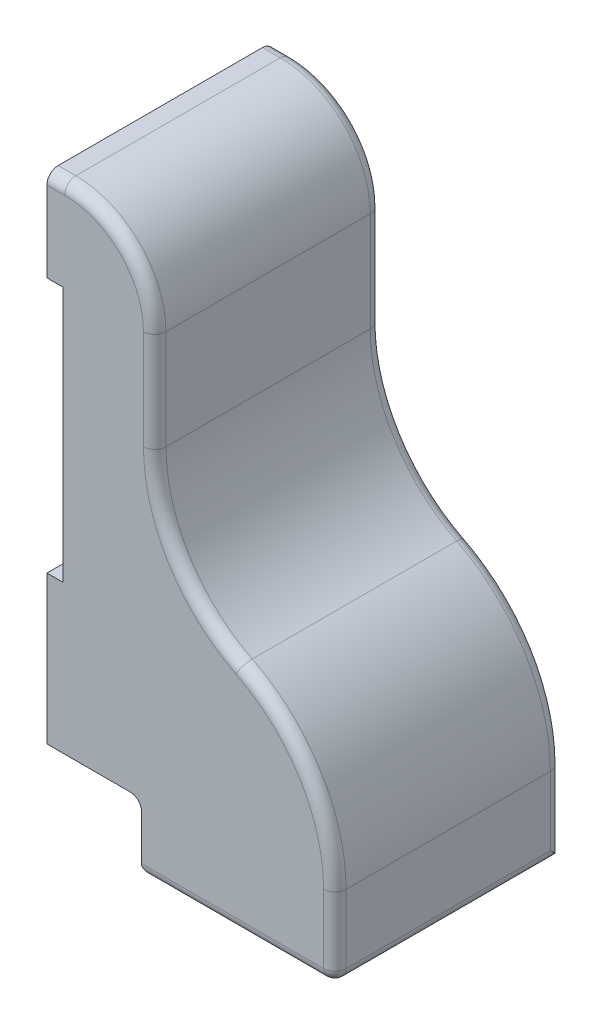
SolidWorks part; units mm, degrees
material "ABS"
ref_plane "X-Y Datum" through (0, 0, 0) normal (0, 0, 1) x (1, 0, 0)
ref_plane "X-Z Datum" through (0, 0, 0) normal (0, 1, 0) x (1, 0, 0)
ref_plane "Y-Z Datum" through (0, 0, 0) normal (1, 0, 0) x (0, 0, -1)
sketch "Sketch1" plane through (0, 0, 0) normal (1, 0, 0) x (0, 0, -1)
  line L0 (100.5047, -7.0485) -> (113.2047, 7.0485)
  line L1 (113.2047, -7.0485) -> (100.5047, 7.0485)
  line L3 (79.8672, -15.875) -> (133.8422, -15.875)
  line L4 (79.8672, -15.875) -> (79.8672, 15.875)
  line L5 (79.8672, 15.875) -> (133.8422, 15.875)
  line L6 (133.8422, -15.875) -> (133.8422, 15.875)
  line L7 (79.8672, -15.875) -> (133.8422, 15.875) construction
  line L8 (79.8672, 15.875) -> (133.8422, -15.875) construction
  point P4 (106.8547, 0)
  dimension "D1" = 31.75
  dimension "D2" = 53.975
extrude "Boss-Extrude1" add sketch "Sketch1" along normal blind 76.2
shell "Shell1" thickness 5
sketch "Sketch2" plane through (0, -20.875, 0) normal (0, -1, 0) x (-1, 0, 0)
  line L0 (-76.2, 133.8422) -> (0, 133.8422) construction
  line L1 (-76.2, 79.8672) -> (-76.2, 133.8422) construction
  line L2 (-76.2, 79.8672) -> (0, 79.8672) construction
  line L3 (-76.2, 133.8422) -> (0, 133.8422)
  line L4 (-76.2, 79.8672) -> (-76.2, 133.8422)
  line L5 (-76.2, 79.8672) -> (0, 79.8672)
  line L6 (-31.75, 79.8672) -> (-31.75, 133.8422)
  dimension "D1" = 44.45
extrude "Cut-Extrude1" cut sketch "Sketch2" against normal blind 5 contours L5 L6 L3 L4
fillet "Fillet2" radius 6.35 1 edges at (31.75, -15.875, -106.8547)
sketch "Sketch3" plane through (0, -20.875, 0) normal (0, -1, 0) x (1, 0, 0)
  line L0 (31.75, -79.8672) -> (31.75, -133.8422) construction
  line L1 (76.2, -79.8672) -> (31.75, -79.8672) construction
  line L2 (76.2, -79.8672) -> (76.2, -133.8422) construction
  line L3 (76.2, -133.8422) -> (31.75, -133.8422) construction
  line L4 (0, -138.8422) -> (81.2, -138.8422)
  line L5 (81.2, -138.8422) -> (81.2, -74.8672)
  line L6 (81.2, -74.8672) -> (0, -74.8672)
  line L7 (0, -74.8672) -> (0, -138.8422)
  line L8 (0, -138.8422) -> (81.2, -138.8422)
  line L9 (81.2, -138.8422) -> (81.2, -74.8672)
  line L10 (81.2, -74.8672) -> (0, -74.8672)
  line L11 (0, -74.8672) -> (0, -138.8422)
  line L12 (76.2, -79.8672) -> (31.75, -79.8672)
  line L13 (31.75, -79.8672) -> (31.75, -133.8422)
  line L14 (76.2, -133.8422) -> (31.75, -133.8422)
  line L15 (76.2, -79.8672) -> (76.2, -133.8422)
  line L16 (26.67, -138.8422) -> (26.67, -74.8672)
  dimension "D2" = 5
  dimension "D3" = 5.08
  dimension "D1" = 0
extrude "Boss-Extrude2" add sketch "Sketch3" along normal blind 19.05
fillet "Fillet5" radius 3.175 1 edges at (26.67, -20.875, -106.8547)
fillet "Fillet6" radius 3.175 2 edges at (26.67, -39.925, -106.8547) (53.935, -39.925, -74.8672)
sketch "Sketch4" plane through (0, 0, 0) normal (1, 0, 0) x (0, 0, -1)
  line L0 (113.2047, -7.0485) -> (100.5047, 7.0485) construction
  line L1 (100.5047, -7.0485) -> (113.2047, 7.0485) construction
  line L2 (113.2047, -7.0485) -> (100.5047, 7.0485)
  line L3 (100.5047, -7.0485) -> (113.2047, 7.0485)
  line L4 (79.8672, -15.875) -> (133.8422, -15.875)
  line L5 (133.8422, -15.875) -> (133.8422, 15.875)
  line L6 (133.8422, 15.875) -> (79.8672, 15.875)
  line L7 (79.8672, 15.875) -> (79.8672, -15.875)
  line L8 (79.8672, -15.875) -> (133.8422, -15.875)
  line L9 (133.8422, -15.875) -> (133.8422, 15.875)
  line L10 (133.8422, 15.875) -> (79.8672, 15.875)
  line L11 (79.8672, 15.875) -> (79.8672, -15.875)
  line L12 (87.2421, 105.9053) -> (126.4673, 105.9053) construction
  line L14 (79.8672, 97.9678) -> (133.8422, 97.9678)
  line L15 (79.8672, 97.9678) -> (79.8672, 113.8428)
  line L16 (79.8672, 113.8428) -> (133.8422, 113.8428)
  line L17 (133.8422, 97.9678) -> (133.8422, 113.8428)
  line L18 (79.8672, 97.9678) -> (133.8422, 113.8428) construction
  line L19 (79.8672, 113.8428) -> (133.8422, 97.9678) construction
  point P10 (106.8547, 105.9053)
  point P15 (0, 0)
  dimension "D2" = 15.875
  dimension "D1" = 0
extrude "Boss-Extrude3" add sketch "Sketch4" along normal blind 25.4 separate body contours L14 L17 L16 L15
shell "Shell2" thickness 5
sketch "Sketch5" plane through (0, 92.9678, 0) normal (0, -1, 0) x (1, 0, 0)
  line L4 (9.525, -74.8672) -> (9.525, -138.8422)
  line L5 (30.4, -138.8422) -> (0, -138.8422) construction
  line L6 (25.4, -133.8422) -> (0, -133.8422) construction
  line L7 (25.4, -133.8422) -> (0, -133.8422)
  line L8 (25.4, -79.8672) -> (25.4, -133.8422) construction
  line L9 (25.4, -79.8672) -> (25.4, -133.8422)
  line L10 (25.4, -79.8672) -> (0, -79.8672) construction
  line L11 (25.4, -79.8672) -> (0, -79.8672)
  line L12 (30.4, -74.8672) -> (0, -74.8672) construction
  point P0 (0, 0)
  dimension "D1" = 15.875
extrude "Cut-Extrude2" cut sketch "Sketch5" against normal blind 5 contours L9 L11 L4 L7
sketch "Sketch6" plane through (0, 92.9678, 0) normal (0, -1, 0) x (1, 0, 0)
  line L0 (30.4, -74.8672) -> (0, -74.8672) construction
  line L1 (30.4, -138.8422) -> (4.525, -138.8422)
  line L2 (30.4, -138.8422) -> (30.4, -74.8672)
  line L3 (30.4, -74.8672) -> (4.525, -74.8672)
  line L4 (4.525, -138.8422) -> (4.525, -74.8672)
  line L5 (9.525, -79.8672) -> (9.525, -133.8422) construction
  line L6 (25.4, -133.8422) -> (9.525, -133.8422) construction
  line L7 (25.4, -79.8672) -> (25.4, -133.8422) construction
  line L8 (25.4, -79.8672) -> (9.525, -79.8672) construction
  line L9 (25.4, -133.8422) -> (9.525, -133.8422)
  line L10 (25.4, -79.8672) -> (25.4, -133.8422)
  line L11 (25.4, -79.8672) -> (9.525, -79.8672)
  line L12 (9.525, -79.8672) -> (9.525, -133.8422)
  line M4 (0, -138.8422) -> (30.4, -138.8422)
  line M5 (30.4, -138.8422) -> (30.4, -74.8672)
  line M6 (30.4, -74.8672) -> (0, -74.8672)
  line M7 (25.4, -79.8672) -> (25.4, -133.8422)
  line M8 (25.4, -133.8422) -> (9.525, -133.8422)
  line M9 (9.525, -133.8422) -> (9.525, -79.8672)
  line M10 (9.525, -79.8672) -> (25.4, -79.8672)
  dimension "D1" = 5
extrude "Boss-Extrude4" add sketch "Sketch6" along normal up to surface (72.0928 mm away) contours L4 M4 M5 M6 M10 M7 M8 M9 up to face at (40.6, 20.875, -106.8547)
sketch "Sketch7" plane through (0, 15.875, 0) normal (0, -1, 0) x (1, 0, 0)
  line L0 (25.4, -133.8422) -> (0, -133.8422) construction
  line L1 (25.4, -79.8672) -> (25.4, -133.8422) construction
  line L2 (25.4, -79.8672) -> (0, -79.8672) construction
  line L3 (9.525, -74.8672) -> (9.525, -138.8422) construction
  line L4 (25.4, -133.8422) -> (0, -133.8422)
  line L5 (25.4, -79.8672) -> (25.4, -133.8422)
  line L6 (25.4, -79.8672) -> (0, -79.8672)
  line L7 (9.525, -74.8672) -> (9.525, -138.8422)
  line M3 (76.2, -79.8672) -> (0, -79.8672)
extrude "Cut-Extrude3" cut sketch "Sketch7" against normal blind 5 contours L7 L4 L5 M3
fillet "Fillet7" radius 44.45 1 edges at (30.4, 20.875, -106.8547)
fillet "Fillet8" radius 46.99 1 edges at (25.4, 15.875, -106.8547)
fillet "Fillet9" radius 46.99 1 edges at (76.2, 15.875, -106.8547)
fillet "Fillet10" radius 48.26 1 edges at (81.2, 20.875, -106.8547)
fillet "Fillet11" radius 6.35 1 edges at (9.525, 15.875, -106.8547)
fillet "Fillet12" radius 6.35 1 edges at (9.525, 97.9678, -106.8547)
fillet "Fillet13" radius 19.05 1 edges at (25.4, 113.8428, -106.8547)
fillet "Fillet14" radius 25.4 1 edges at (30.4, 118.8428, -106.8547)
fillet "Fillet15" radius 3.175 14 edges at (81.2, -28.6482, -138.8422) (30.4, 79.3839, -74.8672) (30.4, 79.3839, -138.8422) (36.9754, 42.0588, -138.8422) (36.9754, 42.0588, -74.8672) (74.061, 7.889, -138.8422) (74.061, 7.889, -74.8672) (2.5, 118.8428, -74.8672) (2.5, 118.8428, -138.8422) (22.9605, 111.4033, -138.8422) (22.9605, 111.4033, -74.8672) (81.2, -39.925, -108.4422) (81.2, -27.0607, -74.8672) (81.2, -38.9951, -75.7971)
